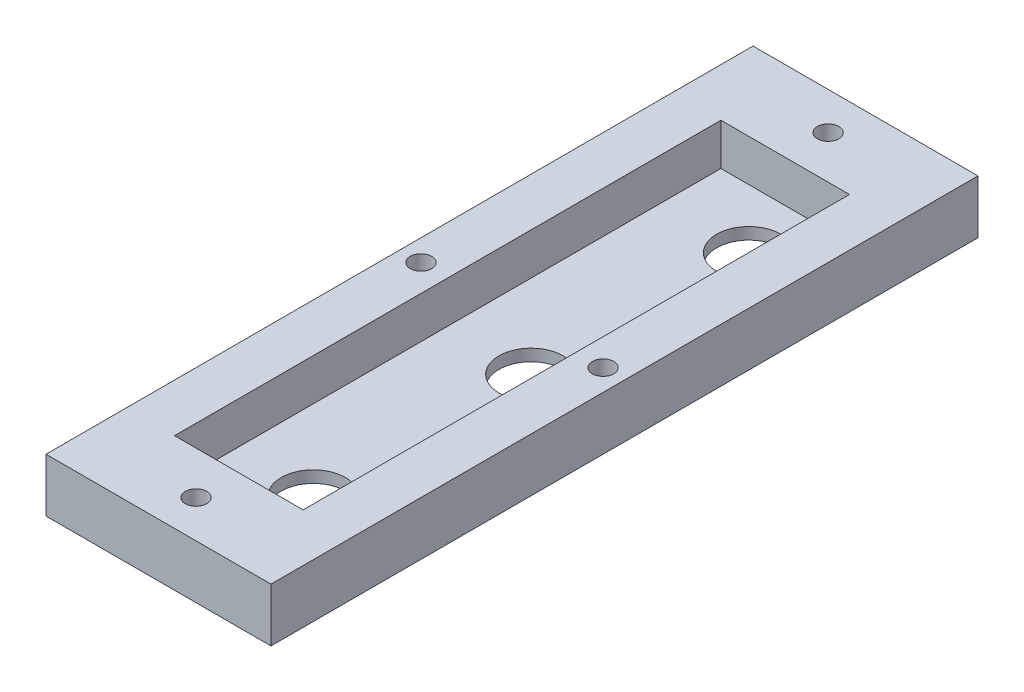
SolidWorks part; units mm, degrees
ref_plane "前视基准面" through (0, 0, 0) normal (0, 0, 1) x (1, 0, 0)
ref_plane "上视基准面" through (0, 0, 0) normal (0, 1, 0) x (1, 0, 0)
ref_plane "右视基准面" through (0, 0, 0) normal (1, 0, 0) x (0, 0, -1)
other "Configuration Table"
sketch "草图1" plane through (0, 0, 0) normal (0, 1, 0) x (1, 0, 0)
  line L5 (-10.5, -33) -> (10.5, -33)
  line L6 (-10.5, -33) -> (-10.5, 33)
  line L15 (-10.5, 33) -> (10.5, 33)
  line L16 (10.5, -33) -> (10.5, 33)
  line L17 (-10.5, -33) -> (10.5, 33) construction
  line L18 (-10.5, 33) -> (10.5, -33) construction
  point P0 (0, 0)
  dimension "D1" = 21
  dimension "D2" = 66
extrude "凸台-拉伸1" add sketch "草图1" along normal blind 1.1
sketch "草图2" plane through (0, 0, 0) normal (0, -1, 0) x (-1, 0, 0)
  circle A0 centre (-1.4583, -20.0033) radius 3
  circle A1 centre (-1.7861, -0.006) radius 3
  circle A2 centre (-2.1138, 19.9913) radius 3
  dimension "D1" = 6
extrude "切除-拉伸1" cut sketch "草图2" against normal through all
sketch "草图3" plane through (0, 1.1, 0) normal (0, 1, 0) x (1, 0, 0)
  line L0 (10.5, 33) -> (-10.5, 33) construction
  line L1 (-6, 25.5) -> (6, 25.5)
  line L2 (-6, 25.5) -> (-6, -25.5)
  line L3 (-6, -25.5) -> (6, -25.5)
  line L4 (6, 25.5) -> (6, -25.5)
  line L5 (-10.5, 33) -> (-10.5, -33) construction
  line L6 (10.5, -33) -> (10.5, 33) construction
  line L7 (-10.5, -33) -> (10.5, -33) construction
  line M8 (10.5, -33) -> (10.5, 33)
  line M9 (10.5, 33) -> (-10.5, 33)
  line M10 (-10.5, 33) -> (-10.5, -33)
  line M11 (-10.5, -33) -> (10.5, -33)
  dimension "D1" = 7.5
  dimension "D2" = 4.5
  dimension "D3" = 4.5
  dimension "D4" = 7.5
extrude "凸台-拉伸2" add sketch "草图3" along normal blind 3.9 contours L1 L4 L3 L2 M11 M8 M9 M10 region at (0, 1.1, 32.3074)
sketch "草图4" plane through (0, 0, 0) normal (0, -1, 0) x (1, 0, 0)
  circle A0 centre (0, 29.5) radius 1
  circle A1 centre (0, 29.5) radius 1.9
  circle A2 centre (-8.5, 0) radius 1.9
  circle A3 centre (-8.5, 0) radius 1
  circle A4 centre (8.5, 0) radius 1.9
  circle A5 centre (8.5, 0) radius 1
  circle A6 centre (0, -29.5) radius 1.9
  circle A7 centre (0, -29.5) radius 1
  point P10 (0, 29.5)
  point P13 (8.5, 0)
  point P14 (-8.5736, 0.8688)
  point P15 (-8.5, 0)
  point P16 (0, -29.5)
  dimension "D1" = 2
  dimension "D2" = 3.8
extrude "切除-拉伸2" cut sketch "草图4" against normal offset from surface (3 mm away) 2 up to face at (0, 5, 0)
extrude "切除-拉伸3" cut sketch "草图4<2>" against normal through all contours A3 | A5 | A0 | A7 region at (-8.5, 0, 0) region at (8.5, 0, 0)
sketch "草图4<2>" plane through (0, 0, 0) normal (0, -1, 0) x (1, 0, 0) same geometry as "草图4"
